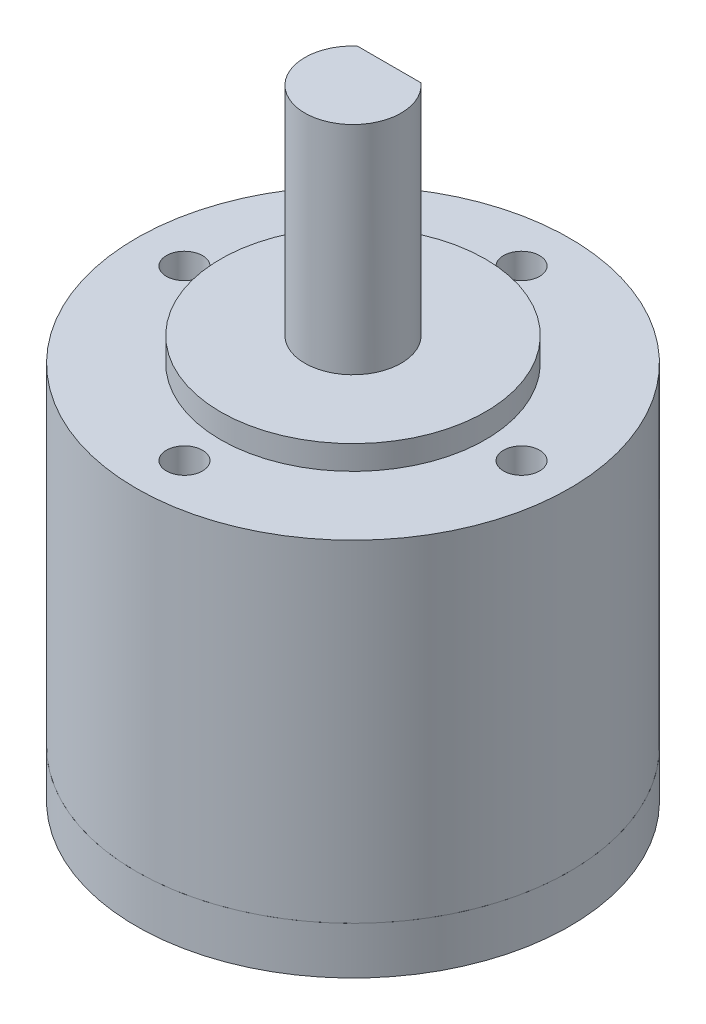
SolidWorks part; units mm, degrees
ref_plane "Front Plane" through (0, 0, 0) normal (0, 0, 1) x (1, 0, 0)
ref_plane "Top Plane" through (0, 0, 0) normal (0, 1, 0) x (1, 0, 0)
ref_plane "Right Plane" through (0, 0, 0) normal (1, 0, 0) x (0, 0, -1)
sketch "Sketch1" plane through (0, 0, 0) normal (0, 1, 0) x (1, 0, 0)
  circle A0 centre (0, 0) radius 18
  dimension "D1" = 36
extrude "Boss-Extrude1" add sketch "Sketch1" along normal mid plane 27.559
sketch "Sketch2" plane through (0, 13.7795, 0) normal (0, 1, 0) x (1, 0, 0)
  circle A0 centre (0, 0) radius 11
  dimension "D1" = 22
extrude "Boss-Extrude2" add sketch "Sketch2" along normal blind 2
sketch "Sketch3" plane through (0, 15.7795, 0) normal (0, 1, 0) x (1, 0, 0)
  circle A0 centre (0, 0) radius 4
  dimension "D1" = 8
extrude "Boss-Extrude4" add sketch "Sketch3" along normal blind 18
sketch "Sketch4" plane through (0, 33.7795, 0) normal (0, 1, 0) x (1, 0, 0)
  line L0 (-2.6458, 3) -> (2.6458, 3)
  line L1 (0, -4) -> (0, 3) construction
  arc A0 (0, -4) -> (2.6458, 3) centre (0, 0) ccw construction
  circle A1 centre (0, 0) radius 4
  arc A2 (2.6458, 3) -> (-2.6458, 3) centre (0, 0) ccw
  arc A3 (-2.6458, 3) -> (0, -4) centre (0, 0) ccw construction
  dimension "D2" = 7
  dimension "D1" = 0
extrude "Cut-Extrude1" cut sketch "Sketch4" against normal blind 15
sketch "Sketch5" plane through (0, 13.7795, 0) normal (0, 1, 0) x (1, 0, 0)
  circle A0 centre (0, 0) radius 14 construction
  circle A1 centre (0, 14) radius 1.5
  circle A2 centre (-14, 0) radius 1.5
  circle A3 centre (0, -14) radius 1.5
  circle A4 centre (14, 0) radius 1.5
  dimension "D1" = 28
  dimension "D2" = 3
extrude "Cut-Extrude2" cut sketch "Sketch5" against normal through all
sketch "Sketch6" plane through (0, -13.7795, 0) normal (0, -1, 0) x (1, 0, 0)
  circle A0 centre (0, 0) radius 11.178
  dimension "D1" = 22.356
extrude "Cut-Extrude3" cut sketch "Sketch6" against normal blind 20
sketch "Sketch7" plane through (0, -13.7795, 0) normal (0, -1, 0) x (1, 0, 0)
  circle A1 centre (0, 0) radius 18
  circle A2 centre (0, 0) radius 18
  dimension "D1" = 0
extrude "Boss-Extrude5" add sketch "Sketch7" along normal blind 3.937 separate body
sketch "Sketch8" plane through (0, -13.7795, 0) normal (0, 1, 0) x (1, 0, 0)
  circle A0 centre (0, 0) radius 10.9855
  dimension "D1" = 21.971
extrude "Boss-Extrude6" add sketch "Sketch8" along normal blind 2.413
sketch "Sketch9" plane through (0, -13.7795, 0) normal (0, 1, 0) x (1, 0, 0)
  circle A0 centre (0, 14) radius 1.265
  circle A1 centre (14, 0) radius 1.265
  circle A2 centre (0, -14) radius 1.265
  circle A3 centre (-14, 0) radius 1.265
  dimension "D1" = 2.53
extrude "Cut-Extrude4" cut sketch "Sketch9" against normal through all
sketch "Sketch10" plane through (0, -11.3665, 0) normal (0, 1, 0) x (1, 0, 0)
  circle A0 centre (0, 0) radius 4
  dimension "D1" = 8
extrude "Cut-Extrude5" cut sketch "Sketch10" against normal through all
sketch "Sketch11" plane through (0, -11.3665, 0) normal (0, 1, 0) x (1, 0, 0)
  circle A0 centre (0, 0) radius 4.75
  dimension "D1" = 9.5
extrude "Cut-Extrude6" cut sketch "Sketch11" against normal blind 0.6
